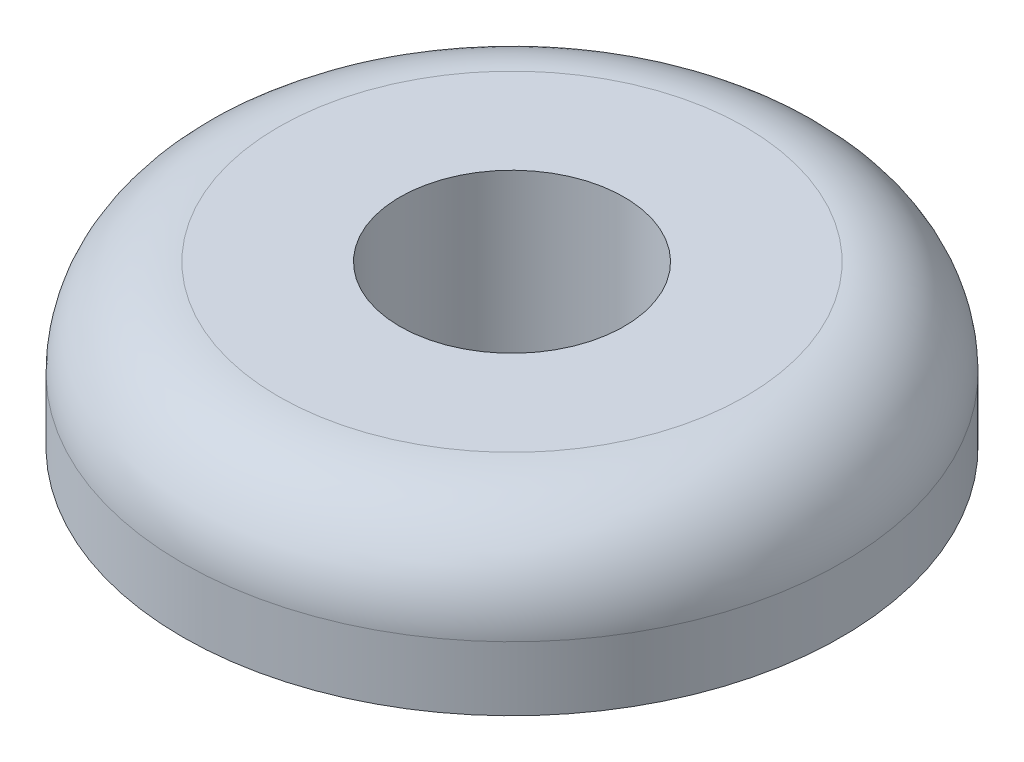
SolidWorks part; units mm, degrees
ref_plane "Front Plane" through (0, 0, 0) normal (0, 0, 1) x (1, 0, 0)
ref_plane "Top Plane" through (0, 0, 0) normal (0, 1, 0) x (1, 0, 0)
ref_plane "Right Plane" through (0, 0, 0) normal (1, 0, 0) x (0, 0, -1)
sketch "Sketch1" plane through (0, 0, 0) normal (0, 1, 0) x (1, 0, 0)
  circle A0 centre (0, 0) radius 12.7 construction
  circle A1 centre (0, 0) radius 3.5
  circle A2 centre (0, 0) radius 10.287
  dimension "D1" = 25.4
  dimension "D2" = 2.413
  dimension "D3" = 7
extrude "Boss-Extrude1" add sketch "Sketch1" along normal blind 5
fillet "Fillet1" radius 3 1 edges at (0, 5, 10.287)
